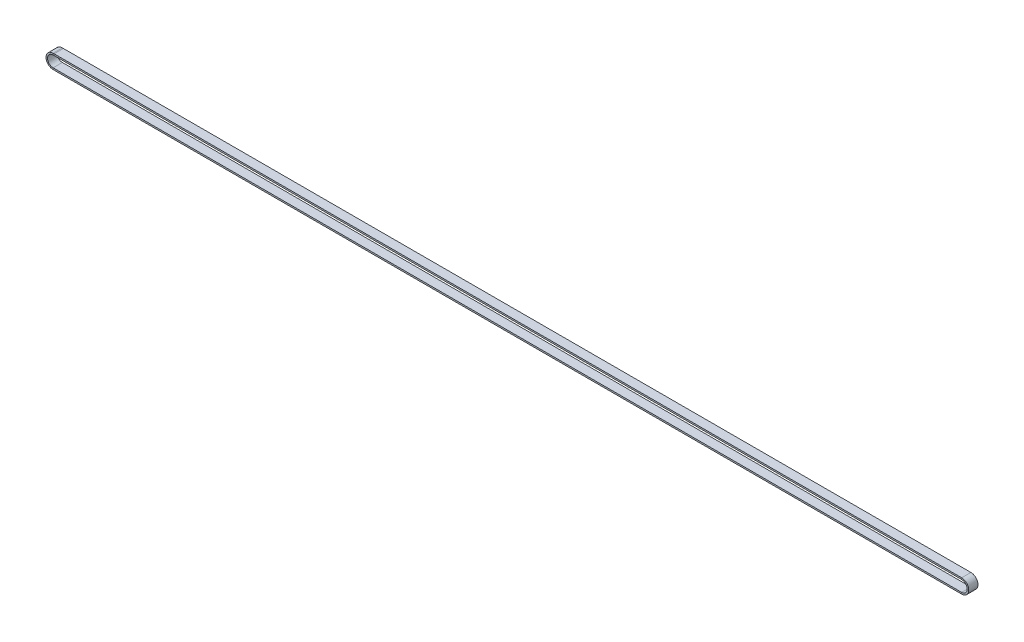
SolidWorks part; units mm, degrees
ref_plane "Front Plane" through (0, 0, 0) normal (0, 0, 1) x (1, 0, 0)
ref_plane "Top Plane" through (0, 0, 0) normal (0, 1, 0) x (1, 0, 0)
ref_plane "Right Plane" through (0, 0, 0) normal (1, 0, 0) x (0, 0, -1)
sketch "Sketch2" plane through (0, 0, 0) normal (0, 0, 1) x (1, 0, 0)
  line L0 (0, 0) -> (1, 0) construction
  line L1 (0, 0) -> (0, 1) construction
  line L2 (-1, -38.0859) -> (883.5206, -38.0859)
  line L3 (883.5206, -51.8859) -> (-1, -51.8859)
  arc A0 (-1, -51.8859) -> (-1, -38.0859) centre (-1, -44.9859) cw
  arc A1 (883.5206, -38.0859) -> (883.5206, -51.8859) centre (883.5206, -44.9859) cw
sketch "Sketch3" plane through (0, 0, 0) normal (1, 0, 0) x (0, 0, -1)
  line L1 (0, -39.5859) -> (-9, -39.5859)
  line L2 (0, -39.5859) -> (0, -38.0859)
  line L3 (0, -38.0859) -> (-9, -38.0859)
  line L4 (-9, -39.5859) -> (-9, -38.0859)
  dimension "D1" = 9
  dimension "D2" = 1.5
sweep "Sweep1" add profiles "Sketch3" path "Sketch2"
